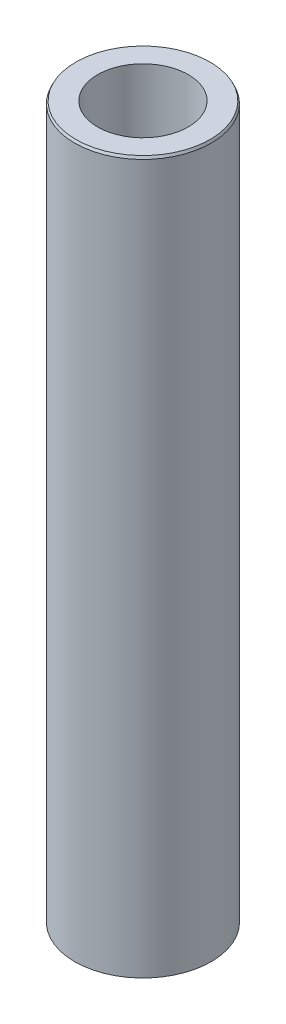
SolidWorks part; units mm, degrees
ref_plane "Front Plane" through (0, 0, 0) normal (0, 0, 1) x (1, 0, 0)
ref_plane "Top Plane" through (0, 0, 0) normal (0, 1, 0) x (1, 0, 0)
ref_plane "Right Plane" through (0, 0, 0) normal (1, 0, 0) x (0, 0, -1)
sketch "Sketch1" plane through (0, 0, 0) normal (0, 1, 0) x (1, 0, 0)
  circle A0 centre (0, 0) radius 57.5
  dimension "SHAFT_OD" = 115
extrude "Boss-Extrude1" add sketch "Sketch1" along normal blind 600
sketch "Sketch2" plane through (0, 0, 0) normal (0, 1, 0) x (1, 0, 0)
  circle A0 centre (0, 0) radius 38.1866
  dimension "BORE_D" = 76.3731
extrude "Cut-Extrude1" cut sketch "Sketch2" along normal through all
chamfer "Chamfer1" distance 2.1233 angle 25.297 2 edges at (0, 600, 57.5) (0, 0, 57.5) first distance on face at (0, 600, 57.5) first distance on face at (0, 0, 38.1866)
